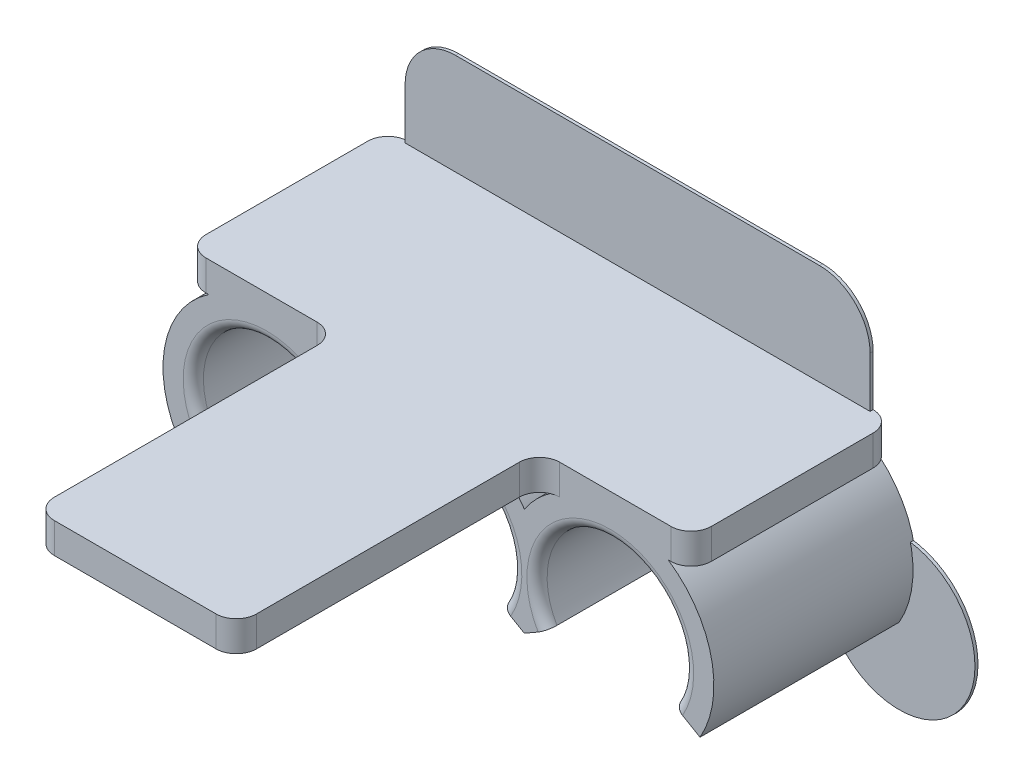
SolidWorks part; units mm, degrees
ref_plane "Front Plane" through (0, 0, 0) normal (0, 0, 1) x (1, 0, 0)
ref_plane "Top Plane" through (0, 0, 0) normal (0, 1, 0) x (1, 0, 0)
ref_plane "Right Plane" through (0, 0, 0) normal (1, 0, 0) x (0, 0, -1)
sketch "Sketch1" plane through (0, 0, 0) normal (0, 0, 1) x (1, 0, 0)
  line L1 (25, -1.5) -> (-25, -1.5)
  line L2 (25, -1.5) -> (25, 1.5)
  line L3 (25, 1.5) -> (-25, 1.5)
  line L4 (-25, -1.5) -> (-25, 1.5)
  line L5 (25, -1.5) -> (-25, 1.5) construction
  line L6 (25, 1.5) -> (-25, -1.5) construction
  point P0 (0, 0)
  dimension "D1" = 3
  dimension "D2" = 50
extrude "Wall mount" add sketch "Sketch1" along normal blind 50
sketch "Sketch3" plane through (0, 0, 0) normal (0, 0, 1) x (1, 0, 0)
  line L0 (-8.5, -14.9075) -> (-6.2787, -13.625)
  line L1 (6.2787, -13.625) -> (8.5, -14.9075)
  line L2 (0, -10) -> (0, -28.1954) construction
  line L3 (8.5, -14.9075) -> (10.7213, -13.625)
  line L4 (23.2787, -13.625) -> (25.8768, -15.125)
  line L5 (17, -10) -> (17, -28.1954) construction
  line L6 (-25.8768, -15.125) -> (-23.2787, -13.625)
  line L7 (-10.7213, -13.625) -> (-8.5, -14.9075)
  line L8 (-17, -10) -> (-17, -28.1954) construction
  line L9 (-22.7282, -1.5) -> (-11.2718, -1.5)
  line L10 (-25, -1.5) -> (25, -1.5) construction
  line L11 (-5.7282, -1.5) -> (5.7282, -1.5)
  line L12 (11.2718, -1.5) -> (22.7282, -1.5)
  arc A0 (6.2787, -13.625) -> (-6.2787, -13.625) centre (0, -10) ccw
  arc A1 (-22.7282, -1.5) -> (-25.8768, -15.125) centre (-17, -10) ccw
  arc A2 (23.2787, -13.625) -> (10.7213, -13.625) centre (17, -10) ccw
  arc A3 (25.8768, -15.125) -> (22.7282, -1.5) centre (17, -10) ccw
  arc A4 (-10.7213, -13.625) -> (-23.2787, -13.625) centre (-17, -10) ccw
  arc A5 (-5.7282, -1.5) -> (-8.5, -4.2718) centre (0, -10) ccw
  arc A6 (8.5, -4.2718) -> (5.7282, -1.5) centre (0, -10) ccw
  arc A7 (-8.5, -4.2718) -> (-11.2718, -1.5) centre (-17, -10) ccw
  arc A9 (11.2718, -1.5) -> (8.5, -4.2718) centre (17, -10) ccw
  dimension "D2" = 14.5
  dimension "D1" = 10
  dimension "D4" = 60
  dimension "D5" = 60
  dimension "D6" = 2
  dimension "D7" = 2
extrude "Boss-Extrude3" add sketch "Sketch3" along normal blind 20
sketch "Sketch4" plane through (0, -1.5, 0) normal (0, -1, 0) x (1, 0, 0)
  line L1 (-25, 50) -> (25, 50) construction
  line L3 (-10, 50) -> (-10, 20)
  line L8 (10, 50) -> (10, 20)
  line L9 (24.25, 20) -> (9.75, 20) construction
  line L10 (-10, 50) -> (-25, 50)
  line L11 (-25, 50) -> (-25, 20)
  line L12 (-25.8768, 20) -> (-23.2787, 20) construction
  line L13 (-25, 50) -> (-25, 0) construction
  line L14 (-25, 20) -> (-10, 20)
  line L15 (10, 50) -> (25, 50)
  line L16 (25, 50) -> (25, 20)
  line L17 (25, 50) -> (25, 0) construction
  line L18 (23.2787, 20) -> (25.8768, 20) construction
  line L19 (25, 20) -> (10, 20)
  dimension "D1" = 20
  dimension "D2" = 10
extrude "Cut-Extrude1" cut sketch "Sketch4" against normal up to next
fillet "Fillet2" radius 2 8 edges at (-25, 0, 0) (25, 0, 0) (25, 0, 20) (10, 0, 20) (-25, 0, 20) (-10, 0, 20) (10, 0, 50) (-10, 0, 50)
fillet "Fillet3" radius 1 3 edges at (17, -2.75, 20) (0, -2.75, 20) (-17, -2.75, 20)
sketch "Sketch5" plane through (0, 0, 0) normal (0, 0, 1) x (1, 0, 0)
  line L0 (-23.2787, -13.625) -> (-18.5283, -13.625)
  line L1 (-23, 1.5) -> (23, 1.5)
  line L2 (-23, 1.5) -> (-23, 6.5)
  line L3 (-18, 11.5) -> (18, 11.5)
  line L4 (23, 1.5) -> (23, 6.5)
  line L5 (-15.8895, -13.625) -> (-1.1105, -13.625)
  line L6 (1.1105, -13.625) -> (15.8895, -13.625)
  line L7 (18.5283, -13.625) -> (23.2787, -13.625)
  arc A0 (-15.8895, -13.625) -> (-1.1105, -13.625) centre (-8.5, -14.9075) ccw
  arc A1 (1.1105, -13.625) -> (15.8895, -13.625) centre (8.5, -14.9075) ccw
  arc A2 (-23.9335, -7.8811) -> (-18.5283, -13.625) centre (-25.8768, -15.125) ccw
  arc A3 (18.5283, -13.625) -> (23.9335, -7.8811) centre (25.8768, -15.125) ccw
  arc A4 (-23.9335, -7.8811) -> (-23.2787, -13.625) centre (-17, -10) ccw
  arc A5 (23.2787, -13.625) -> (23.9335, -7.8811) centre (17, -10) ccw
  arc A6 (23, 6.5) -> (18, 11.5) centre (18, 6.5) ccw
  arc A7 (-18, 11.5) -> (-23, 6.5) centre (-18, 6.5) ccw
  point P33 (-23, 11.5)
  dimension "D1" = 15
  dimension "D2" = 15
  dimension "D3" = 15
  dimension "D4" = 15
  dimension "D6" = 5
  dimension "D5" = 10
extrude "Boss-Extrude4" add sketch "Sketch5" along normal blind 0.3 separate body
